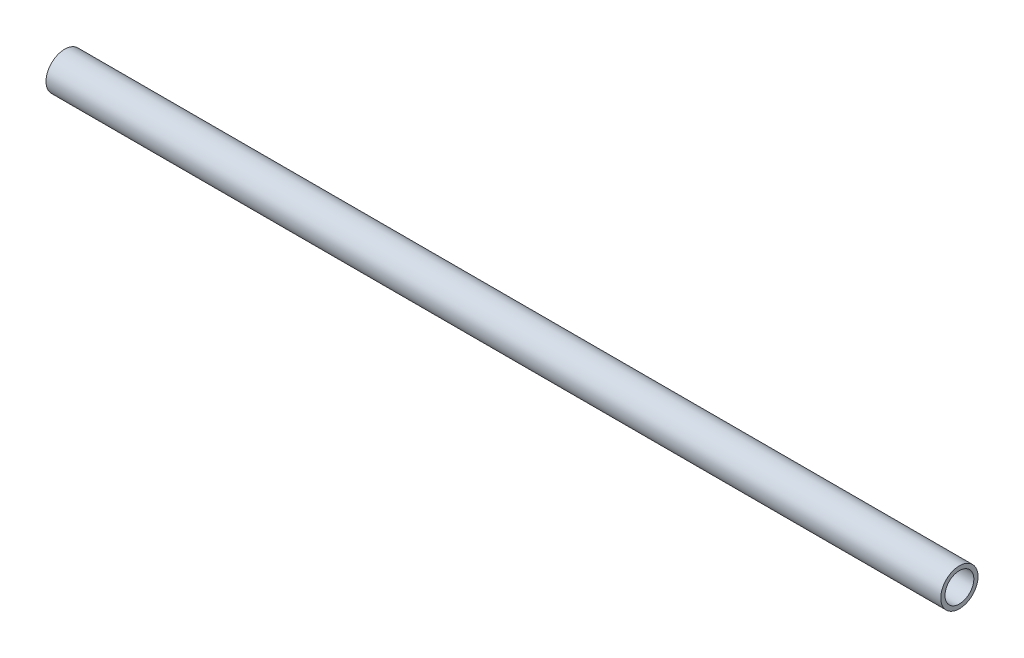
SolidWorks part; units mm, degrees
ref_plane "Front Plane" through (0, 0, 0) normal (0, 0, 1) x (1, 0, 0)
ref_plane "Top Plane" through (0, 0, 0) normal (0, 1, 0) x (1, 0, 0)
ref_plane "Right Plane" through (0, 0, 0) normal (1, 0, 0) x (0, 0, -1)
sketch "Sketch2" plane through (0, 0, 0) normal (1, 0, 0) x (0, 0, -1)
  circle A0 centre (0, 0) radius 12.7
  circle A1 centre (0, 0) radius 9.8298
  dimension "D1" = 25.4
  dimension "D2" = 2.8702
extrude "Boss-Extrude1" add sketch "Sketch2" along normal blind 609.6
